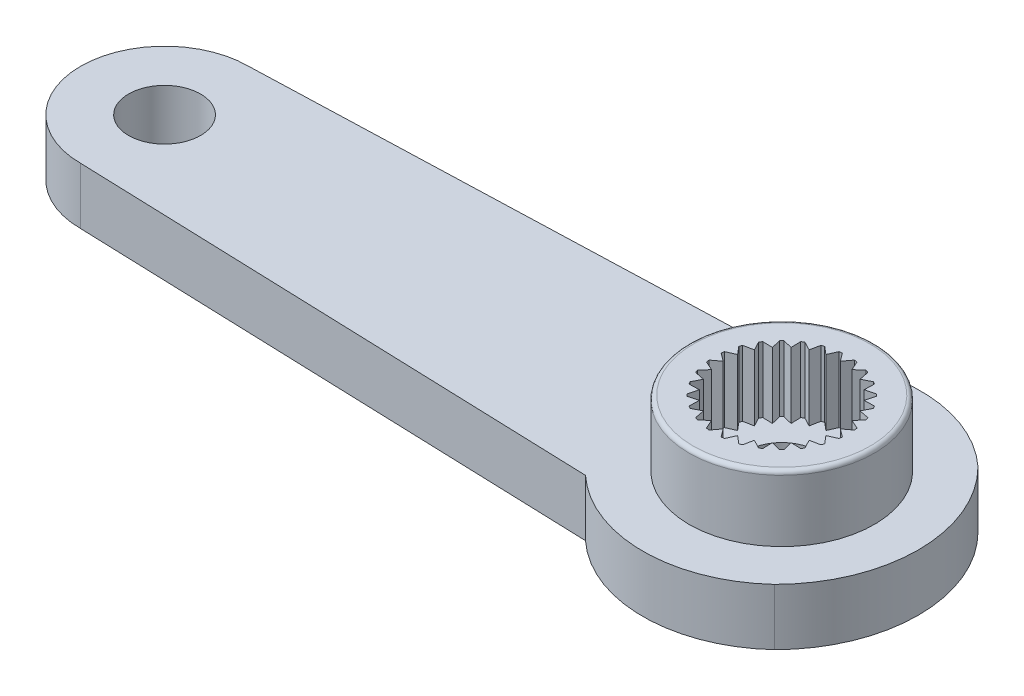
SolidWorks part; units mm, degrees
ref_plane "Alzado" through (0, 0, 0) normal (0, 0, 1) x (1, 0, 0)
ref_plane "Planta" through (0, 0, 0) normal (0, 1, 0) x (1, 0, 0)
ref_plane "Vista lateral" through (0, 0, 0) normal (1, 0, 0) x (0, 0, -1)
sketch "Sketch1" plane through (0, 0, 0) normal (0, 1, 0) x (1, 0, 0)
  line L2 (0, -55) -> (0, 55) construction
  line L9 (-30, 4.0824) -> (-4.5891, 4.95)
  line L10 (-30, -4.0824) -> (-4.5891, -4.95)
  arc A0 (-4.5891, -4.95) -> (4.5891, -4.95) centre (0, 0) ccw
  arc A3 (4.5891, 4.95) -> (-4.5891, 4.95) centre (0, 0) ccw
  circle A4 centre (0, 0) radius 1.7
  arc A15 (4.5891, 4.95) -> (4.5891, -4.95) centre (-0.3609, 0) cw
  circle A16 centre (-30, 0) radius 1.75
  arc A19 (-30, -4.0824) -> (-30, 4.0824) centre (-30, 0) cw
  dimension "D1" = 13.5
  dimension "D3" = 30
  dimension "D5" = 3.4
  dimension "D2" = 3.5
  dimension "D4" = 9.9
extrude "Boss-Extrude1" add sketch "Sketch1" along normal blind 2.75
sketch "Sketch2" plane through (0, 2.75, 0) normal (0, 1, 0) x (1, 0, 0)
  circle A0 centre (0, 0) radius 3.25
  circle A1 centre (0, 0) radius 4.5
  dimension "D1" = 6.5
  dimension "D2" = 9
extrude "Boss-Extrude2" add sketch "Sketch2" along normal blind 3.2
sketch "Sketch3" plane through (0, 5.95, 0) normal (0, 1, 0) x (1, 0, 0)
  line L0 (-0.3, 3.25) -> (0.3, 3.25)
  line L1 (-0.3, 3.25) -> (0, 2.85)
  line L2 (0, 2.85) -> (0.3, 3.25)
  circle A1 centre (0, 0) radius 3.25 construction
  circle A2 centre (0, 0) radius 3.25 construction
  point P3 (0, 3.25)
  point P6 (0.3, 3.25)
  dimension "D1" = 0.4
  dimension "D2" = 0.6
extrude "Boss-Extrude3" add sketch "Sketch3" against normal up to surface (3.2 mm away) up to face at (0, 2.75, 1.7)
pattern_circular "CirPattern1" count 28 over 360 about axis through (0, 2.75, 0) along (0, 1, 0) of "Boss-Extrude3"
sketch "Sketch4" plane through (0, 0, 0) normal (0, -1, 0) x (1, 0, 0)
  circle A0 centre (0, 0) radius 3
  circle A1 centre (0, 0) radius 3.5
  circle A2 centre (0, 0) radius 4.5
  circle M10 centre (0, 0) radius 1.7
  dimension "D1" = 6
  dimension "D2" = 0.5
  dimension "D3" = 1
extrude "Cut-Extrude1" cut sketch "Sketch4" against normal blind 1 contours A0 M10 | A2 A1 region at (-2.9151, 0, 0) region at (-4.3727, 0, 0)
fillet "Fillet1" radius 0.25 3 edges at (0, 0, -3.5) (0, 0, -3) (0, 0, -4.5)
fillet "Fillet2" radius 0.2 1 edges at (0, 5.95, 4.5)
